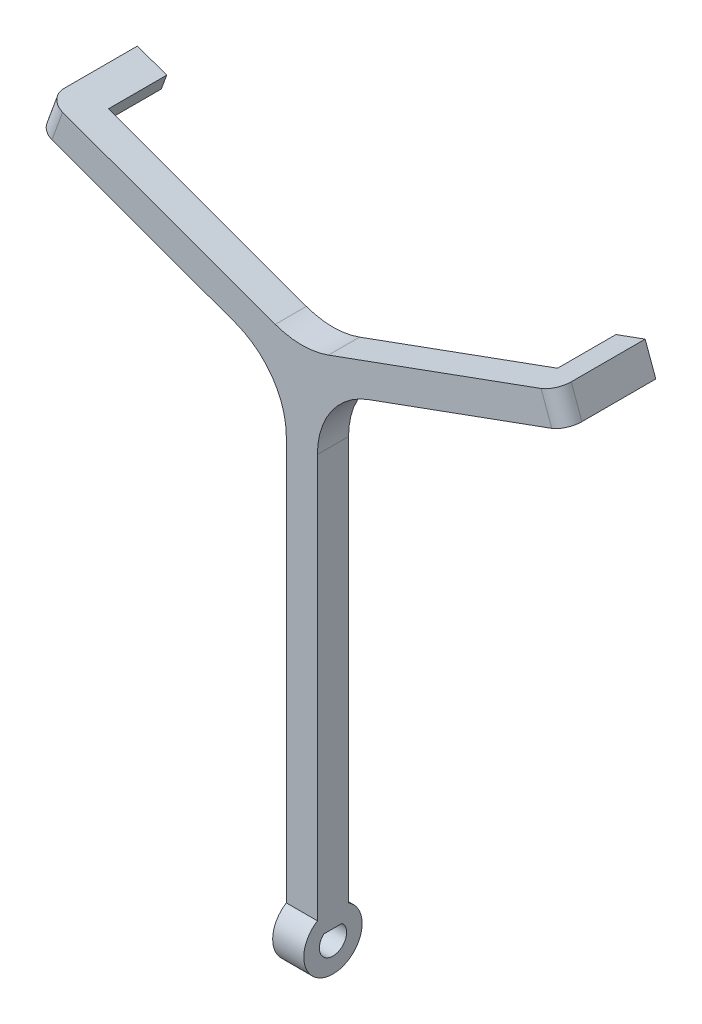
SolidWorks part; units mm, degrees
material "PLA"
ref_plane "Plan de face" through (0, 0, 0) normal (0, 0, 1) x (1, 0, 0)
ref_plane "Plan de dessus" through (0, 0, 0) normal (0, 1, 0) x (1, 0, 0)
ref_plane "Plan de droite" through (0, 0, 0) normal (1, 0, 0) x (0, 0, -1)
sketch "Esquisse1" plane through (0, 0, 0) normal (0, 0, 1) x (1, 0, 0)
  line L1 (0, 0) -> (136, 0) construction
  line L2 (0, 0) -> (0, 155) construction
  line L3 (0, 155) -> (136, 155) construction
  line L4 (136, 0) -> (136, 155) construction
  line L16 (64, 0) -> (64, 124.1884)
  line L17 (64, 124.1884) -> (0, 147.4825)
  line L18 (0, 147.4825) -> (2.7362, 155)
  line L19 (2.7362, 155) -> (68, 131.2459)
  line L20 (68, 131.2459) -> (133.2638, 155)
  line L21 (133.2638, 155) -> (136, 147.4825)
  line L22 (136, 147.4825) -> (72, 124.1884)
  line L23 (72, 124.1884) -> (72, 0)
  line L24 (72, 0) -> (64, 0)
  point P19 (68, 0)
  dimension "D1" = 136
  dimension "D2" = 155
  dimension "D3" = 8
  dimension "D4" = 68
  dimension "D5" = 110
  dimension "D6" = 110
  dimension "D7" = 140
  dimension "D8" = 8
  dimension "D9" = 8
  dimension "D10" = 68
extrude "Boss.-Extru.1" add sketch "Esquisse1" along normal blind 8
sketch "Esquisse2" plane through (0, 0, 0) normal (0, 0, -1) x (-1, 0, 0)
  line L0 (-72, 124.1884) -> (-136, 147.4825) construction
  line L1 (-136, 147.4825) -> (-133.2638, 155) construction
  line L2 (-133.2638, 155) -> (-68, 131.2459) construction
  line L3 (-132.2412, 146.1144) -> (-136, 147.4825)
  line L4 (-136, 147.4825) -> (-133.2638, 155)
  line L5 (-133.2638, 155) -> (-125.7463, 152.2638)
  line L6 (-127.1144, 148.5051) -> (-125.7463, 152.2638)
  line L7 (0, 147.4825) -> (-64, 124.1884) construction
  line L8 (-68, 131.2459) -> (-2.7362, 155) construction
  line L9 (-2.7362, 155) -> (0, 147.4825) construction
  line L10 (0, 147.4825) -> (-3.7588, 146.1144)
  line L11 (-10.2537, 152.2638) -> (-2.7362, 155)
  line L12 (-2.7362, 155) -> (0, 147.4825)
  line L13 (-10.2537, 152.2638) -> (-8.8856, 148.5051)
  line L14 (-132.2412, 146.1144) -> (-127.1144, 148.5051)
  line L15 (-8.8856, 148.5051) -> (-3.7588, 146.1144)
  dimension "D2" = 8
  dimension "D1" = 8
  dimension "D3" = 4
  dimension "D4" = 4
  dimension "D5" = 4
  dimension "D6" = 4
extrude "Boss.-Extru.2" add sketch "Esquisse2" along normal blind 15
fillet "Congé1" radius 20 3 edges at (72, 124.1884, 4) (64, 124.1884, 4) (68, 131.2459, 4)
fillet "Congé2" radius 4 2 edges at (134.6319, 151.2412, 8) (1.3681, 151.2412, 8)
sketch "Esquisse3" plane through (64, 0, 0) normal (-1, 0, 0) x (0, 0, 1)
  line L0 (4, 0) -> (4, 33.6289) construction
  line L1 (8, 0) -> (0, 0) construction
  circle A0 centre (4, 0) radius 7.5
  dimension "D1" = 15
extrude "Boss.-Extru.3" add sketch "Esquisse3" against normal up to surface (8 mm away) up to face at (72, 55.0921, 4)
sketch "Esquisse4" plane through (64, 0, 0) normal (-1, 0, 0) x (0, 0, 1)
  line L7 (4, 0) -> (4, 7.4852) construction
  line L11 (1.6569, 2.6) -> (6.3431, 2.6)
  line L12 (0.3981, -3.5) -> (8.2082, -3.5) construction
  arc A1 (1.6569, 2.6) -> (6.3431, 2.6) centre (4, 0) ccw
  point P10 (4, 6)
  point P11 (4, 6)
  dimension "D1" = 7
  dimension "D2" = 6.1
extrude "Enlèv. mat.-Extru.1" cut sketch "Esquisse4" against normal through all
equation "\"long_tot\"=155"
equation "\"espac_sub_arms\"= 120"
equation "\"épaiss_cadre\"=8"
equation "\"long_protub\"= 15"
equation "\"rayon_conge\"= 3"
equation "\"diam_axe\"= 5"
equation "\"D1@Esquisse1\"=\"espac_sub_arms\"+\"épaiss_cadre\"*2"
equation "\"D2@Esquisse1\"=\"long_tot\""
equation "\"D3@Esquisse1\"=\"épaiss_cadre\""
equation "\"D4@Esquisse1\"=\"D1@Esquisse1\"/2"
equation "\"D6@Esquisse1\"=\"D5@Esquisse1\""
equation "\"D8@Esquisse1\"=\"épaiss_cadre\""
equation "\"D9@Esquisse1\"=\"épaiss_cadre\""
equation "\"D10@Esquisse1\"=\"D4@Esquisse1\""
equation "\"D1@Boss.-Extru.1\"=\"épaiss_cadre\""
equation "\"D2@Esquisse2\"=\"épaiss_cadre\""
equation "\"D1@Boss.-Extru.2\"=\"long_protub\""
equation "\"D1@Esquisse2\"=\"épaiss_cadre\""
equation "\"D3@Esquisse2\"=\"D1@Esquisse2\"/2"
equation "\"D4@Esquisse2\"=\"D1@Esquisse2\"/2"
equation "\"D5@Esquisse2\"=\"D2@Esquisse2\"/2"
equation "\"D6@Esquisse2\"=\"D2@Esquisse2\"/2"
